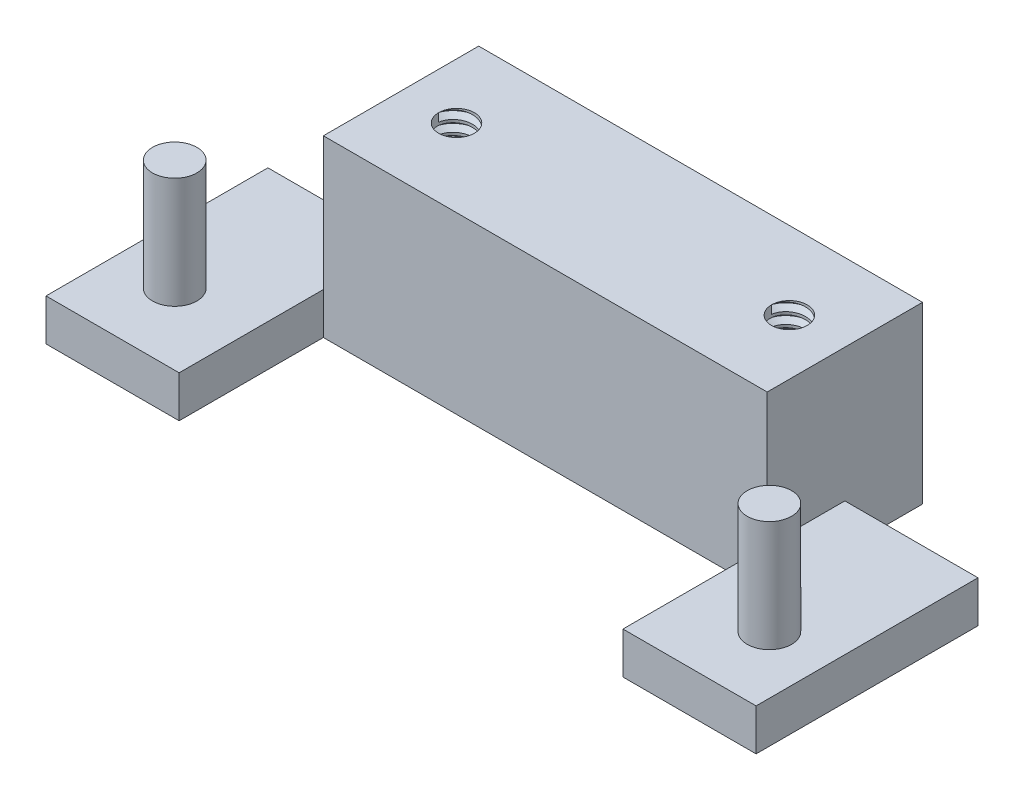
SolidWorks part; units mm, degrees
ref_plane "Front Plane" through (0, 0, 0) normal (0, 0, 1) x (1, 0, 0)
ref_plane "Top Plane" through (0, 0, 0) normal (0, 1, 0) x (1, 0, 0)
ref_plane "Right Plane" through (0, 0, 0) normal (1, 0, 0) x (0, 0, -1)
sketch "Sketch1" plane through (0, 0, 0) normal (0, 1, 0) x (1, 0, 0)
  line L1 (-12.846, 5.1579) -> (12.554, 5.1579)
  line L2 (-12.846, 5.1579) -> (-12.846, -3.7321)
  line L3 (-12.846, -3.7321) -> (12.554, -3.7321)
  line L4 (12.554, 5.1579) -> (12.554, -3.7321)
  dimension "D1" = 25.4
  dimension "D2" = 8.89
extrude "Boss-Extrude1" add sketch "Sketch1" along normal blind 10 contours L1 L4 L3 L2
sketch "Sketch2" plane through (0, 10, 0) normal (0, 1, 0) x (1, 0, 0)
  line L0 (-0.146, 5.1579) -> (-0.146, -3.7321) construction
  line L1 (-12.846, 5.1579) -> (12.554, 5.1579) construction
  line L2 (-12.846, -3.7321) -> (12.554, -3.7321) construction
  line L3 (9.379, 0.7129) -> (-9.671, 0.7129) construction
  circle A0 centre (-9.671, 0.7129) radius 1.0223
  circle A1 centre (9.379, 0.7129) radius 1.0223
  point P10 (-0.146, 0.7129)
  dimension "D2" = 2.0447
  dimension "D1" = 9.525
extrude "Cut-Extrude1" cut sketch "Sketch2" against normal blind 5.08
sketch "Sketch3" plane through (0, 0, 0) normal (0, -1, 0) x (1, 0, 0)
  line L0 (-0.146, -5.1579) -> (-0.146, 3.7321) construction
  line L1 (-12.846, -5.1579) -> (12.554, -5.1579) construction
  line L2 (-12.846, 3.7321) -> (12.554, 3.7321) construction
  circle A0 centre (-0.146, -0.7129) radius 2.9972
  dimension "D1" = 5.9944
extrude "Cut-Extrude2" cut sketch "Sketch3" against normal blind 8
thread "Thread1" pitch 1 method cut profile "Thread Profile2" start angle 0, offset 0, length 0, pitch 1, diameter 5.9944
ref_plane "Plane2" through (2.8512, 0, -0.7129) normal (0, 0, 1) x (1, 0, 0)
sketch "Thread Profile2" plane through (2.8512, 0, -0.7129) normal (0, 0, 1) x (1, 0, 0)
  line L0 (0, 0) -> (0, 1) construction
  line L1 (0, 0) -> (0.5413, 0.3125)
  line L2 (0.5413, 0.3125) -> (0.5413, 0.4375)
  line L3 (0.5413, 0.4375) -> (0, 0.75)
  line L4 (0.5413, 0.375) -> (0, 0.375) construction
  line L11 (0, 0) -> (0, 0.75)
  point P2 (0, 0)
  dimension "Pitch" = 1
  dimension "Profile_Angle" = 60
  dimension "Profile_Land" = 0.125
  dimension "Profile_Height" = 0.5413
thread "Thread2" pitch 0.635 method cut profile "Thread Profile3" start angle 0, offset 0, length 0, pitch 0.635, diameter 2.0447
ref_plane "Plane3" through (-10.6933, 10, -0.7129) normal (0, 0, 1) x (-1, 0, 0)
sketch "Thread Profile3" plane through (-10.6933, 10, -0.7129) normal (0, 0, 1) x (-1, 0, 0)
  line L0 (0, 0) -> (0, 0.635) construction
  line L1 (0, 0) -> (0.3437, 0.1984)
  line L2 (0.3437, 0.1984) -> (0.3437, 0.2778)
  line L3 (0.3437, 0.2778) -> (0, 0.4762)
  line L4 (0.3437, 0.2381) -> (0, 0.2381) construction
  line L11 (0, 0) -> (0, 0.4762)
  point P2 (0, 0)
  dimension "Pitch" = 0.635
  dimension "Profile_Angle" = 60
  dimension "Profile_Land" = 0.0794
  dimension "Profile_Height" = 0.3437
thread "Thread3" pitch 0.635 method cut profile "Thread Profile4" start angle 0, offset 0, length 0, pitch 0.635, diameter 2.0447
ref_plane "Plane4" through (8.3567, 10, -0.7129) normal (0, 0, 1) x (-1, 0, 0)
sketch "Thread Profile4" plane through (8.3567, 10, -0.7129) normal (0, 0, 1) x (-1, 0, 0)
  line L0 (0, 0) -> (0, 0.635) construction
  line L1 (0, 0) -> (0.3437, 0.1984)
  line L2 (0.3437, 0.1984) -> (0.3437, 0.2778)
  line L3 (0.3437, 0.2778) -> (0, 0.4762)
  line L4 (0.3437, 0.2381) -> (0, 0.2381) construction
  line L11 (0, 0) -> (0, 0.4762)
  point P2 (0, 0)
  dimension "Pitch" = 0.635
  dimension "Profile_Angle" = 60
  dimension "Profile_Land" = 0.0794
  dimension "Profile_Height" = 0.3437
sketch "Sketch4" plane through (12.554, 0, 0) normal (1, 0, 0) x (0, 0, -1)
  line L5 (0.7129, 10) -> (0.7129, 2.38) construction
  line L6 (5.1579, 10) -> (-3.7321, 10) construction
  line L8 (0.7129, 2.38) -> (-11.9871, 2.38)
  line L9 (0.7129, 2.38) -> (0.7129, 0)
  line L10 (0.7129, 0) -> (-11.9871, 0)
  line L11 (-11.9871, 2.38) -> (-11.9871, 0)
  dimension "D1" = 7.62
  dimension "D2" = 2.38
  dimension "D3" = 12.7
extrude "Boss-Extrude2" add sketch "Sketch4" along normal blind 7.62
sketch "Sketch5" plane through (0, 2.38, 0) normal (0, 1, 0) x (1, 0, 0)
  line L0 (12.554, -11.9871) -> (16.872, -11.9871) construction
  line L1 (20.174, -11.9871) -> (12.554, -11.9871) construction
  line L2 (16.872, -11.9871) -> (16.872, -7.9231) construction
  line L3 (-0.146, -3.7321) -> (16.872, -3.7321) construction
  line L4 (-12.846, -3.7321) -> (12.554, -3.7321) construction
  circle A0 centre (16.872, -7.9231) radius 1.27
  dimension "D2" = 2.54
  dimension "D1" = 4.318
  dimension "D3" = 4.064
  dimension "D4" = 17.018
extrude "Boss-Extrude3" add sketch "Sketch5" along normal blind 6.35 contours A0
ref_plane "Plane5" through (-0.146, 0, 0) normal (-1, 0, 0) x (0, 0, 1)
mirror "Mirror1" about plane through (-0.146, 0, 0) normal (-1, 0, 0) of "Boss-Extrude2", "Boss-Extrude3"
